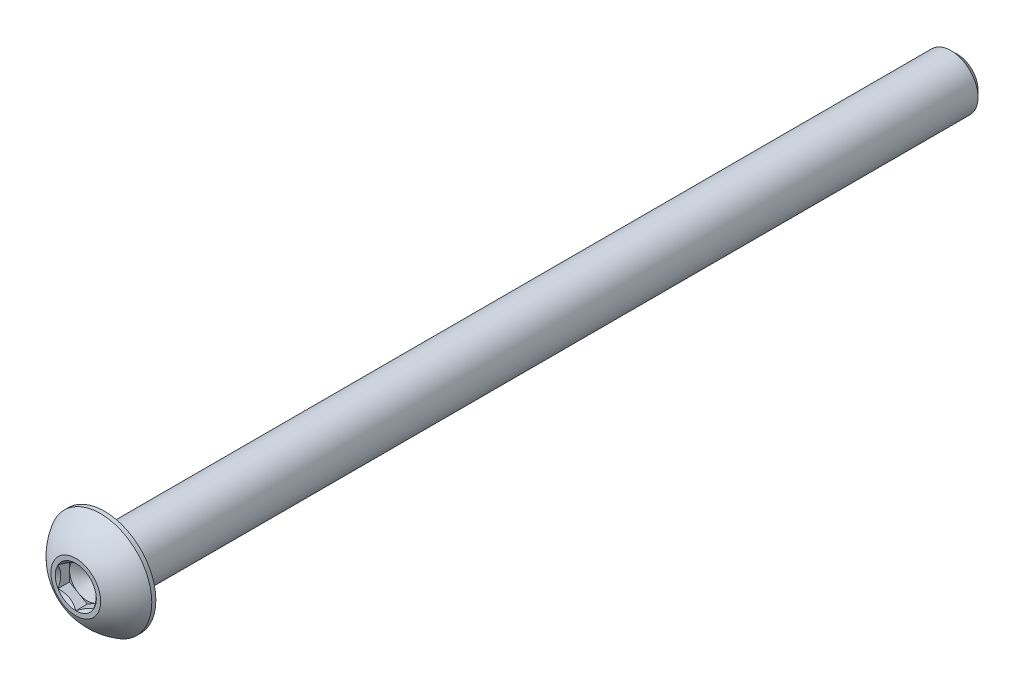
SolidWorks part; units mm, degrees
ref_plane "Front Plane" through (0, 0, 0) normal (0, 0, 1) x (1, 0, 0)
ref_plane "Top Plane" through (0, 0, 0) normal (0, 1, 0) x (1, 0, 0)
ref_plane "Right Plane" through (0, 0, 0) normal (1, 0, 0) x (0, 0, -1)
sketch "Sketch1" plane through (0, 0, 0) normal (1, 0, 0) x (0, 0, -1)
  line L0 (-39.3827, 0) -> (39.3827, 0) construction
  line L1 (-36.8173, 4.5847) -> (-36.8173, -4.5847) construction
  line L2 (-39.3827, 1.5875) -> (-39.3827, -1.5875) construction
  line L3 (39.3827, 2.413) -> (39.3827, -2.413) construction
  line L4 (39.3331, 2.4989) -> (39.73, 1.8115) construction
  line L5 (39.73, 1.8115) -> (40.1268, 2.4989) construction
  line L6 (40.1268, 2.4989) -> (39.3331, 2.4989) construction
  line L7 (39.73, 2.4989) -> (39.73, 2.413) construction
  line L8 (39.73, 1.8115) -> (39.73, 1.8974) construction
  line L9 (39.6804, 1.8974) -> (39.7796, 1.8974)
  line L10 (-39.3827, 2.2225) -> (-39.3827, -2.2225) construction
  line L11 (-36.8173, 4.5847) -> (-37.1802, 4.5847) construction
  line L12 (-39.3827, 1.5875) -> (-38.3565, 1.5875) construction
  line L13 (-38.3565, 1.5875) -> (-37.44, 0) construction
  point P5 (-36.8173, 0)
  point P10 (36.6046, -2.413)
  dimension "Drive Size" = 3.175
  dimension "Head Diameter" = 9.1694
  dimension "Head Height" = 2.5654
  dimension "Screw Size Decimal Equivalent" = 4.826
  dimension "Length" = 76.2
  dimension "D1" = 2.7781
  dimension "Pitch" = 0.7937
  dimension "D2" = 0.0992
  dimension "D3" = 4.445
  dimension "D4" = 0.3629
  dimension "D5" = 60
  dimension "D6" = 1.0262
sketch "Sketch2" plane through (0, 0, 0) normal (1, 0, 0) x (0, 0, -1)
  line L0 (-39.3827, 1.5875) -> (-39.3827, 2.2225)
  line L1 (-37.1802, 4.5847) -> (-36.8173, 4.5847)
  line L2 (-36.8173, 4.5847) -> (-36.8173, 2.413)
  line L3 (-36.8173, 4.5847) -> (-36.8173, -4.5847) construction
  line L4 (-36.8173, 2.413) -> (38.7874, 2.413)
  line L5 (39.3827, 1.8177) -> (39.3827, 0)
  line L6 (-39.3827, 1.5875) -> (-38.3565, 1.5875)
  line L7 (-38.3565, 1.5875) -> (-37.44, 0)
  line L8 (39.3827, 0) -> (-37.44, 0)
  line L9 (38.7874, 2.413) -> (39.3827, 1.8177)
  line L10 (38.7874, -2.413) -> (38.7874, 2.413) construction
  arc A0 (-37.1802, 4.5847) -> (-39.3827, 2.2225) centre (-34.6311, 0) ccw
  point P13 (39.3827, 2.413)
  point P25 (38.7874, 0)
  dimension "D1" = 0.5953
  dimension "D2" = 45
revolve "Revolve1" add sketch "Sketch2" angle 360 about L0
sketch "Sketch3" plane through (0, 0, 0) normal (0, 0, 1) x (1, 0, 0)
  line L1 (0, 1.8331) -> (-1.5875, 0.9165)
  line L2 (-1.5875, 0.9165) -> (-1.5875, -0.9165)
  line L3 (-1.5875, -0.9165) -> (0, -1.8331)
  line L4 (0, -1.8331) -> (1.5875, -0.9165)
  line L5 (1.5875, -0.9165) -> (1.5875, 0.9165)
  line L6 (1.5875, 0.9165) -> (0, 1.8331)
  circle A0 centre (0, 0) radius 1.5875 construction
extrude "Cut-Extrude1" cut sketch "Sketch3" along normal through all from vertex starting at point (0, 1.5875, 38.3565)
sketch "Sketch4" plane through (0, 0, 39.3827) normal (0, 0, 1) x (1, 0, 0)
  circle A0 centre (0, 0) radius 1.8331
extrude "Cut-Extrude2" cut sketch "Sketch4" against normal up to next (78.7654 mm away) draft 45
sketch "Sketch9" plane through (0, 0, 0) normal (1, 0, 0) x (0, 0, -1)
  line L0 (39.3827, -2.413) -> (-36.8173, -2.413) construction
  line L1 (-36.8173, -2.413) -> (38.7874, -2.413) construction
  line L2 (39.3827, -1.8177) -> (39.3827, 1.8177) construction
  line L3 (-36.8173, -2.413) -> (-36.8173, 2.413) construction
  point P9 (38.1921, -2.413)
  dimension "D1" = 1.1906
sketch "Sketch5" [suppressed] plane through (0, 0, -39.3827) normal (0, 0, -1) x (-1, 0, 0)
  circle A0 centre (0, 0) radius 2.413
ref_axis "Center Axis1" through (0, 0, -7.843) along (0, 0, 1)
ref_plane "Contact Plane1" through (0, 0, -39.3827) normal (0, 0, 1) x (1, 0, 0)
ref_plane "Contact Plane2" through (0, 0, 36.8173) normal (0, 0, 1) x (1, 0, 0)
curve "Helix/Spiral1" [suppressed] pitch 0.7937 height 76.9938 turns 97
sketch "Sketch6" [suppressed] plane through (0, 0, 0) normal (1, 0, 0) x (0, 0, -1)
  line L0 (39.3827, 2.413) -> (40.0772, 2.413)
  line L1 (40.0772, 2.413) -> (39.7796, 1.8974)
  line L2 (39.6804, 1.8974) -> (39.7796, 1.8974)
  line L3 (39.6804, 1.8974) -> (39.3827, 2.413)
  line L4 (39.73, 1.8115) -> (40.1268, 2.4989) construction
sweep "Cut-Sweep1" [suppressed] cut profiles "Sketch6" path "Helix/Spiral1"
sketch "Sketch7" [suppressed] plane through (0, 0, 0) normal (1, 0, 0) x (0, 0, -1)
  line L0 (-38.3565, 2.413) -> (-36.8173, 2.413)
  line L1 (-38.3565, 2.413) -> (-38.3565, 1.5875)
  line L2 (-38.3565, 1.5875) -> (-37.44, 0)
  line L3 (-37.44, 0) -> (-35.1647, 0)
  line L5 (-36.8173, 4.5847) -> (-36.8173, -4.5847) construction
  line L6 (-36.8173, 2.413) -> (-35.1647, 1.8115)
  line L7 (-35.1647, 1.8115) -> (-35.1647, 0)
  dimension "D1" = 20
revolve "Revolve2" [suppressed] add sketch "Sketch7" angle 360 about L0
equation "\"D2@Sketch1\"=\"Pitch@Sketch1\"*.125"
equation "\"D1@Sketch1\"=\"Pitch@Sketch1\"*3.5"
equation "\"D3@Sketch1\"=\"Drive Size@Sketch1\"*1.4"
equation "\"D4@Sketch1\"=(\"D3@Sketch1\"-\"Drive Size@Sketch1\")/3.5"
equation "\"D6@Sketch1\"=\"Head Height@Sketch1\"*.40"
equation "\"D1@Sketch2\"=\"Pitch@Sketch1\"*.750"
equation "\"D4@Helix/Spiral1\"=\"Pitch@Sketch1\""
equation "\"D3@Helix/Spiral1\" = \"D4@Helix/Spiral1\" + \"Length@Sketch1\""
equation "\"D1@Sketch9\"=\"Pitch@Sketch1\"*1.5"
